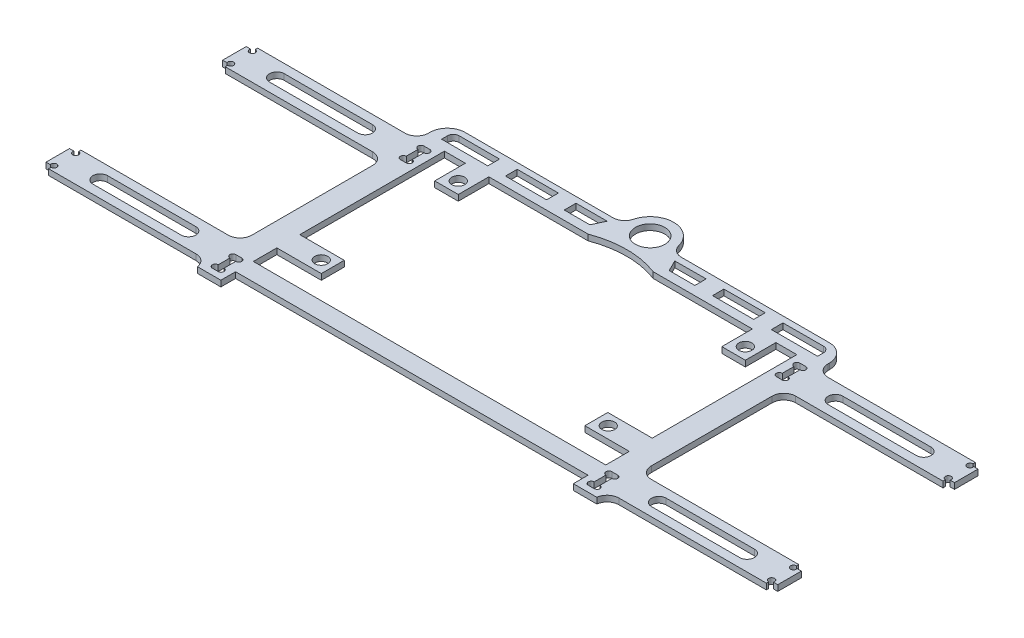
SolidWorks part; units mm, degrees
ref_plane "前视基准面" through (0, 0, 0) normal (0, 0, 1) x (1, 0, 0)
ref_plane "上视基准面" through (0, 0, 0) normal (0, 1, 0) x (1, 0, 0)
ref_plane "右视基准面" through (0, 0, 0) normal (1, 0, 0) x (0, 0, -1)
other "Configuration Table"
sketch "草图1" plane through (0, 0, 0) normal (0, 1, 0) x (1, 0, 0)
  line L235 (-7.9822, 5.6382) -> (-7.9822, -13.4007) construction
  line L271 (-7.9822, 25.5058) -> (-7.9822, 15.0528) construction
  line L312 (-34.9406, 5.0613) -> (13.9856, 5.0613) construction
  line L321 (-37.9406, 20.0528) -> (-37.9406, 17.0528)
  line L344 (52.0197, 21.8522) -> (53.0197, 21.8522)
  line L354 (-37.9406, 16.5528) -> (-37.9406, 17.0528)
  line L361 (25.9761, 23.1228) -> (25.9761, 22.1062)
  line L375 (-41.9406, -15.4472) -> (-37.9406, -15.4472)
  line L376 (-37.9406, -15.4472) -> (-37.9406, -12.9472)
  line L377 (21.9761, -15.4472) -> (21.9761, -12.9472)
  line L378 (25.9761, -15.4472) -> (21.9761, -15.4472)
  line L379 (25.9761, -13.9302) -> (25.9761, -15.4472)
  line L387 (-41.9406, -13.9302) -> (-41.9406, -15.4472)
  line L393 (-37.9406, 16.5528) -> (-37.9406, -2.0302)
  line L394 (21.9761, 16.5528) -> (21.9761, 20.5528)
  line L403 (-37.9406, 20.5528) -> (-37.9406, 20.0528)
  line L420 (-69.9842, 21.1022) -> (-69.4842, 21.1022)
  line L424 (-69.9842, 17.1022) -> (-69.4842, 17.1022)
  line L435 (-69.9842, -12.9302) -> (-69.4842, -12.9302)
  line L436 (-69.9842, -8.9302) -> (-69.4842, -8.9302)
  line L440 (-41.9406, 22.1062) -> (-41.9406, 23.1228)
  line L456 (-41.9406, 16.3522) -> (-41.9406, -8.1842)
  line L457 (25.9761, 16.3522) -> (25.9761, -8.1842)
  line L458 (21.9761, 16.5528) -> (21.9761, -2.0302)
  line L459 (-41.9406, 23.1228) -> (-41.9406, 27.0728)
  line L461 (25.9761, 27.0728) -> (25.9761, 23.1228)
  line L462 (52.0197, 16.3522) -> (53.0197, 16.3522)
  line L464 (52.0197, 21.8522) -> (25.9761, 21.8522)
  line L465 (25.9761, 21.8522) -> (25.9761, 22.1062)
  line L466 (52.0197, 16.3522) -> (25.9761, 16.3522)
  line L468 (-67.9842, 16.3522) -> (-41.9406, 16.3522)
  line L469 (-67.9842, 21.8522) -> (-41.9406, 21.8522)
  line L470 (-69.9842, -8.9302) -> (-70.1842, -8.9302)
  line L471 (-70.1842, -8.9302) -> (-70.1842, -12.9302)
  line L474 (-41.9406, 21.8522) -> (-41.9406, 22.1062)
  line L475 (-37.9406, 20.5528) -> (-37.9406, 21.5528)
  line L477 (-69.4842, -8.9302) -> (-69.4611, -8.9302)
  line L478 (-69.9842, -12.9302) -> (-69.9842, -13.6802) construction
  line L479 (-67.9842, -13.6802) -> (-41.9406, -13.6802)
  line L480 (-41.9406, -13.6802) -> (-41.9406, -13.9302)
  line L481 (-67.4842, -8.1842) -> (-41.9406, -8.1842)
  line L483 (-67.9842, -8.1842) -> (-67.4842, -8.1842)
  line L485 (52.0197, -13.6802) -> (25.9761, -13.6802)
  line L486 (51.5197, -8.1842) -> (25.9761, -8.1842)
  line L488 (52.0197, -8.1842) -> (51.5197, -8.1842)
  line L490 (25.9761, -13.6802) -> (25.9761, -13.9302)
  line L491 (21.9761, 21.5528) -> (21.9761, 20.5528)
  line L498 (-37.9406, 21.5528) -> (-37.9406, 22.5528)
  line L499 (-37.9406, 22.5528) -> (-34.3822, 22.5528)
  line L500 (21.9761, 22.5528) -> (21.9761, 21.5528)
  line L505 (18.4178, 22.5528) -> (21.9761, 22.5528)
  line L506 (-30.3822, 22.5528) -> (-14.7875, 22.5528)
  line L507 (-37.9406, -8.9302) -> (-37.9406, -9.9302)
  line L510 (21.9761, -9.9302) -> (21.9761, -8.9302)
  line L517 (-1.1769, 22.5528) -> (14.4178, 22.5528)
  line L518 (-41.9406, 27.0728) -> (-11.9508, 27.0728)
  line L519 (-4.0136, 27.0728) -> (25.9761, 27.0728)
  line L528 (21.9761, -6.7302) -> (21.9761, -8.9302)
  line L530 (-37.9406, -6.7302) -> (-37.9406, -8.9302)
  line L536 (-37.9406, -5.9302) -> (-37.9406, -6.7302)
  line L540 (21.9761, -5.9302) -> (21.9761, -6.7302)
  line L541 (-40.4406, 21.5698) -> (-39.4406, 21.5698)
  line L542 (-39.4406, 20.5698) -> (-39.4406, 18.5698)
  line L544 (-40.4406, 20.5698) -> (-40.4406, 18.5698)
  line L557 (-67.9842, 21.8522) -> (-68.9842, 21.8522)
  line L559 (-67.9842, 16.3522) -> (-68.9842, 16.3522)
  line L562 (-68.9842, -8.1842) -> (-67.9842, -8.1842)
  line L563 (-67.9842, -13.6802) -> (-68.9842, -13.6802)
  line L565 (54.0197, -8.9302) -> (54.2197, -8.9302)
  line L566 (54.2197, -8.9302) -> (54.2197, -12.9302)
  line L569 (54.0197, 17.1022) -> (53.5197, 17.1022)
  line L571 (54.0197, 21.1022) -> (53.5197, 21.1022)
  line L572 (54.0197, -12.9302) -> (54.0197, -13.6802) construction
  line L573 (54.0197, -8.9302) -> (54.0197, -8.1802) construction
  line L575 (52.0197, -13.6802) -> (53.0197, -13.6802)
  line L576 (53.0197, -8.1842) -> (52.0197, -8.1842)
  line L578 (54.0197, -8.9302) -> (53.5197, -8.9302)
  line L579 (54.0197, -12.9302) -> (53.5197, -12.9302)
  line L581 (-69.9842, 21.1022) -> (-70.1842, 21.1022)
  line L582 (-70.1842, 21.1022) -> (-70.1842, 17.1022)
  line L583 (-70.1842, 17.1022) -> (-69.9842, 17.1022)
  line L584 (-70.1842, -12.9302) -> (-69.9842, -12.9302)
  line L585 (54.0197, 21.1022) -> (54.2197, 21.1022)
  line L586 (54.2197, 21.1022) -> (54.2197, 17.1022)
  line L587 (54.2197, 17.1022) -> (54.0197, 17.1022)
  line L588 (54.2197, -12.9302) -> (54.0197, -12.9302)
  line L590 (53.4955, 21.1022) -> (53.5197, 21.1022)
  line L591 (53.5197, 17.1022) -> (53.4968, 17.1022)
  line L593 (53.0198, 21.1022) -> (53.0198, 20.9482) construction
  line L595 (53.5197, -8.9302) -> (53.4968, -8.9302)
  line L596 (53.5197, -12.9302) -> (53.4968, -12.9302)
  line L597 (-69.4842, -12.9302) -> (-69.4611, -12.9302)
  line L600 (-69.4842, 21.1022) -> (-69.4611, 21.1022)
  line L602 (-69.4842, 17.1022) -> (-69.4599, 17.1024)
  line L635 (-40.4406, 17.8607) -> (-40.4406, 18.0698) construction
  line L636 (23.4761, 21.5698) -> (24.4761, 21.5698)
  line L637 (-40.4406, 17.5698) -> (-39.4406, 17.5698)
  line L638 (24.4761, 20.5698) -> (24.4761, 18.5698)
  line L639 (23.4761, 20.5698) -> (23.4761, 18.5698)
  line L640 (23.4761, 17.5698) -> (24.4761, 17.5698)
  line L641 (23.4761, -10.4057) -> (24.4761, -10.4057)
  line L642 (24.4761, -11.4057) -> (24.4761, -13.4057)
  line L643 (23.4761, -11.4057) -> (23.4761, -13.4057)
  line L644 (23.4761, -14.4057) -> (24.4761, -14.4057)
  line L645 (-40.4406, -10.4057) -> (-39.4406, -10.4057)
  line L646 (-39.4406, -11.4057) -> (-39.4406, -13.4057)
  line L647 (-40.4406, -11.4057) -> (-40.4406, -13.4057)
  line L648 (-40.4406, -14.4057) -> (-39.4406, -14.4057)
  line L649 (-37.9406, -9.9302) -> (21.9761, -9.9302)
  line L650 (21.9761, -12.9472) -> (-37.9406, -12.9472)
  line L652 (18.4178, 22.5528) -> (18.4178, 17.3528)
  line L653 (18.4178, 17.3528) -> (14.4178, 17.3528)
  line L654 (14.4178, 17.3528) -> (14.4178, 22.5528)
  line L656 (-34.3822, 22.5528) -> (-34.3822, 17.3528)
  line L657 (-34.3822, 17.3528) -> (-30.3822, 17.3528)
  line L658 (-30.3822, 17.3528) -> (-30.3822, 22.5528)
  line L659 (-37.9406, -2.0302) -> (-30.5822, -2.0302)
  line L660 (-30.5822, -2.0302) -> (-30.3822, -2.0302)
  line L661 (-30.3822, -2.0302) -> (-30.3822, -5.9302)
  line L662 (-30.3822, -5.9302) -> (-37.9406, -5.9302)
  line L663 (21.9761, -2.0302) -> (14.4178, -2.0302)
  line L664 (14.4178, -2.0302) -> (14.4178, -5.9302)
  line L665 (14.4178, -5.9302) -> (21.9761, -5.9302)
  line L666 (-14.7875, 22.5528) -> (-13.5106, 22.5528)
  line L667 (-2.4539, 22.5528) -> (-1.1769, 22.5528)
  line L668 (53.0197, 21.8522) -> (53.0198, 21.4482)
  line L669 (53.0198, 16.7522) -> (53.0197, 16.3522)
  line L670 (53.0197, -8.1842) -> (53.0197, -8.5802)
  line L672 (53.0197, -13.2802) -> (53.0197, -13.6802)
  line L674 (-68.9842, 21.8522) -> (-68.9842, 21.4522)
  line L675 (-68.9842, 16.7562) -> (-68.9842, 16.3522)
  line L676 (-68.9842, -8.1842) -> (-68.9842, -8.5802)
  line L677 (-68.9842, -13.2802) -> (-68.9842, -13.6802)
  circle A36 centre (-7.9822, 27.5728) radius 2.5
  circle A58 centre (-32.3822, 19.3528) radius 1.1
  circle A59 centre (16.4178, 19.3528) radius 1.1
  circle A60 centre (-32.3822, -3.9472) radius 1.1
  circle A61 centre (16.4178, -3.9472) radius 1.1
  arc A77 (-4.0136, 27.0728) -> (-11.9508, 27.0728) centre (-7.9822, 27.5728) ccw
  arc A99 (53.0198, 21.4482) -> (53.4955, 21.1022) centre (53.0198, 20.9482) ccw
  arc A100 (53.4968, 17.1022) -> (53.0198, 16.7522) centre (53.0198, 17.2522) ccw
  arc A101 (53.0197, -8.5802) -> (53.4968, -8.9302) centre (53.0198, -9.0802) ccw
  arc A102 (53.4968, -12.9302) -> (53.0197, -13.2802) centre (53.0198, -12.7802) ccw
  arc A103 (-69.4611, -8.9302) -> (-68.9842, -8.5802) centre (-68.9842, -9.0802) ccw
  arc A104 (-68.9842, -13.2802) -> (-69.4611, -12.9302) centre (-68.9842, -12.7802) ccw
  arc A105 (-69.4611, 21.1022) -> (-68.9842, 21.4522) centre (-68.9842, 20.9522) ccw
  arc A106 (-68.9842, 16.7562) -> (-69.4599, 17.1024) centre (-68.9842, 17.2562) ccw
  arc A107 (-40.4406, 21.5698) -> (-40.4406, 20.5698) centre (-40.4406, 21.0698) ccw
  arc A108 (-39.4406, 20.5698) -> (-39.4406, 21.5698) centre (-39.4406, 21.0698) ccw
  arc A109 (-40.4406, 18.5698) -> (-40.4406, 17.5698) centre (-40.4406, 18.0698) ccw
  arc A110 (-39.4406, 17.5698) -> (-39.4406, 18.5698) centre (-39.4406, 18.0698) ccw
  arc A111 (23.4761, 21.5698) -> (23.4761, 20.5698) centre (23.4761, 21.0698) ccw
  arc A112 (24.4761, 20.5698) -> (24.4761, 21.5698) centre (24.4761, 21.0698) ccw
  arc A113 (23.4761, 18.5698) -> (23.4761, 17.5698) centre (23.4761, 18.0698) ccw
  arc A114 (24.4761, 17.5698) -> (24.4761, 18.5698) centre (24.4761, 18.0698) ccw
  arc A115 (23.4761, -10.4057) -> (23.4761, -11.4057) centre (23.4761, -10.9057) ccw
  arc A116 (24.4761, -11.4057) -> (24.4761, -10.4057) centre (24.4761, -10.9057) ccw
  arc A117 (23.4761, -13.4057) -> (23.4761, -14.4057) centre (23.4761, -13.9057) ccw
  arc A118 (24.4761, -14.4057) -> (24.4761, -13.4057) centre (24.4761, -13.9057) ccw
  arc A119 (-40.4406, -10.4057) -> (-40.4406, -11.4057) centre (-40.4406, -10.9057) ccw
  arc A120 (-39.4406, -11.4057) -> (-39.4406, -10.4057) centre (-39.4406, -10.9057) ccw
  arc A121 (-40.4406, -13.4057) -> (-40.4406, -14.4057) centre (-40.4406, -13.9057) ccw
  arc A122 (-39.4406, -14.4057) -> (-39.4406, -13.4057) centre (-39.4406, -13.9057) ccw
  arc A124 (-2.4539, 22.5528) -> (-13.5106, 22.5528) centre (-7.9822, 8.0722) ccw
  point P141 (-7.9822, 16.3528)
extrude "凸台-拉伸1" add sketch "草图1" along normal blind 1 contours L488 L486 L457 L466 L464 L465 L361 L461 L519 L518 L459 L440 L474 L469 L420 L424 L468 L456 L481 L483 L436 L435 L479 L480 L387 L375 L376 L377 L378 region at (52.5197, 0, -20.5222)
sketch "草图7" plane through (0, 1, 0) normal (0, 1, 0) x (1, 0, 0)
  line L0 (-39.9406, 26.0728) -> (-32.0853, 26.0728)
  line L1 (-13.7917, 26.0728) -> (-14.7299, 24.0728)
  line L2 (-55.4624, 21.8522) -> (-55.4624, 16.3522) construction
  line L4 (-39.9406, 26.0728) -> (-39.9406, 24.0728)
  line L5 (-39.9406, 24.0728) -> (-37.4406, 24.0728)
  line L8 (-7.9822, 35.4244) -> (-7.9822, 31.0728) construction
  line L10 (23.9761, 24.0728) -> (21.4761, 24.0728)
  line L11 (23.9761, 26.0728) -> (23.9761, 24.0728)
  line L12 (23.9761, 26.0728) -> (16.1208, 26.0432)
  line L14 (-2.1992, 25.974) -> (-1.2497, 24.0728)
  line L15 (-68.9842, 21.8522) -> (-41.9406, 21.8522) construction
  line L16 (-36.0614, -8.9302) -> (-36.0614, -13.9302) construction
  line L19 (-37.4406, 24.0728) -> (-32.0853, 24.0728)
  line L20 (-1.2497, 24.0728) -> (3.1208, 24.0728)
  line L21 (-37.9406, -8.9302) -> (-34.1822, -8.9302) construction
  line L22 (-67.9842, -13.9302) -> (-41.9406, -13.9302) construction
  line L23 (-68.9842, 16.3522) -> (-41.9406, 16.3522) construction
  line L24 (-47.9624, 19.1022) -> (-62.9624, 19.1022) construction
  line L29 (-55.4624, -8.1842) -> (-55.4624, -13.6802) construction
  line L32 (-47.9624, 17.8562) -> (-62.9624, 17.8562)
  line L36 (-47.9624, 20.3482) -> (-62.9624, 20.3482)
  line L37 (-68.9842, -8.1842) -> (-41.9406, -8.1842) construction
  line L38 (-68.9842, -13.6802) -> (-41.9406, -13.6802) construction
  line L39 (-47.9624, -10.9322) -> (-62.9624, -10.9322) construction
  line L40 (39.4979, -8.1842) -> (39.4979, -13.6802) construction
  line L41 (-47.9624, -12.1802) -> (-62.9624, -12.1802)
  line L42 (-47.9624, -9.6842) -> (-62.9624, -9.6842)
  line L43 (39.4979, 21.8522) -> (39.4979, 16.3522) construction
  line L44 (31.9979, -10.9322) -> (46.9979, -10.9322) construction
  line L45 (31.9979, -12.1802) -> (46.9979, -12.1802)
  line L46 (31.9979, -9.6842) -> (46.9979, -9.6842)
  line L47 (31.9979, 19.1022) -> (46.9979, 19.1022) construction
  line L48 (31.9979, 17.8562) -> (46.9979, 17.8562)
  line L49 (31.9979, 20.3482) -> (46.9979, 20.3482)
  line L50 (-26.0853, 24.0728) -> (-22.0853, 24.0728)
  line L51 (-22.0853, 24.0728) -> (-22.0853, 26.0728)
  line L53 (-19.0853, 26.0728) -> (-19.0853, 24.0728)
  line L54 (-26.0853, 24.0728) -> (-29.0853, 24.0728)
  line L55 (-29.0853, 24.0728) -> (-29.0853, 26.0728)
  line L56 (-19.0853, 26.0728) -> (-13.7917, 26.0728)
  line L57 (-32.0853, 26.0728) -> (-32.0853, 24.0728)
  line L58 (-29.0853, 26.0728) -> (-22.0853, 26.0728)
  line L59 (-29.0853, 24.0728) -> (-22.0853, 24.0728)
  line L60 (-19.0853, 24.0728) -> (-14.7299, 24.0728)
  line L61 (3.1208, 26.0728) -> (3.1208, 24.0728)
  line L62 (6.1208, 24.0728) -> (6.1208, 26.0728)
  line L63 (13.1208, 24.0728) -> (13.1208, 26.0728)
  line L64 (16.1208, 26.0728) -> (16.1208, 24.0728)
  line L65 (3.1208, 25.9941) -> (-2.1992, 25.974)
  line L66 (6.1208, 24.0728) -> (13.1208, 24.0728)
  line L67 (13.1208, 26.0319) -> (6.1208, 26.0054)
  line L68 (16.1208, 24.0728) -> (21.4761, 24.0728)
  arc A11 (-47.9624, 17.8562) -> (-47.9624, 20.3482) centre (-47.9624, 19.1022) ccw
  arc A12 (-62.9624, 20.3482) -> (-62.9624, 17.8562) centre (-62.9624, 19.1022) ccw
  arc A13 (-47.9624, -12.1802) -> (-47.9624, -9.6842) centre (-47.9624, -10.9322) ccw
  arc A14 (-62.9624, -9.6842) -> (-62.9624, -12.1802) centre (-62.9624, -10.9322) ccw
  arc A15 (31.9979, -12.1802) -> (31.9979, -9.6842) centre (31.9979, -10.9322) cw
  arc A16 (46.9979, -9.6842) -> (46.9979, -12.1802) centre (46.9979, -10.9322) cw
  arc A17 (31.9979, 17.8562) -> (31.9979, 20.3482) centre (31.9979, 19.1022) cw
  arc A18 (46.9979, 20.3482) -> (46.9979, 17.8562) centre (46.9979, 19.1022) cw
  point P26 (-55.4624, 19.1022)
  point P43 (-55.4624, -10.9322)
  point P52 (39.4979, -10.9322)
  point P63 (39.4979, 19.1022)
fillet "圆角1" radius 3 2 edges at (25.9761, 0.5, -27.0728) (-41.9406, 0.5, -27.0728)
fillet "圆角2" radius 2 8 edges at (25.9761, 0.5, 13.6802) (25.9761, 0.5, 8.1842) (25.9761, 0.5, -16.3522) (25.9761, 0.5, -21.8522) (-41.9406, 0.5, 8.1842) (-41.9406, 0.5, 13.6802) (-41.9406, 0.5, -16.3522) (-41.9406, 0.5, -21.8522)
extrude "切除-拉伸2" cut sketch "草图7" against normal blind 10 contours L36 A12 L32 A11 | L42 A14 L41 A13 | L57 L0 L4 L5 L19 | L58 L55 L54 L50 L51 | L53 L60 L1 L56 | L61 L65 L14 L20 | L63 L67 L62 L66 | L64 L68 L10 L11 L12 | A18 L49 A17 L48 | A16 L46 A15 L45 region at (-36.0129, 1, -25.0728) region at (-16.6654, 1, -25.1053) region at (20.0583, 1, -25.0654) region at (0.6942, 1, -25.0598) region at (-55.4624, 1, -19.1022) region at (-55.4624, 1, 10.9322) region at (39.4979, 1, 10.9322) region at (39.4979, 1, -19.1022) region at (-25.5853, 1, -25.0728) region at (9.6287, 1, -25.0458)
fillet "圆角3" radius 2 2 edges at (-4.0136, 0.5, -27.0728) (-11.9508, 0.5, -27.0728)
fillet "圆角4" radius 1 2 edges at (23.9761, 0.5, -26.0728) (-39.9406, 0.5, -26.0728)
